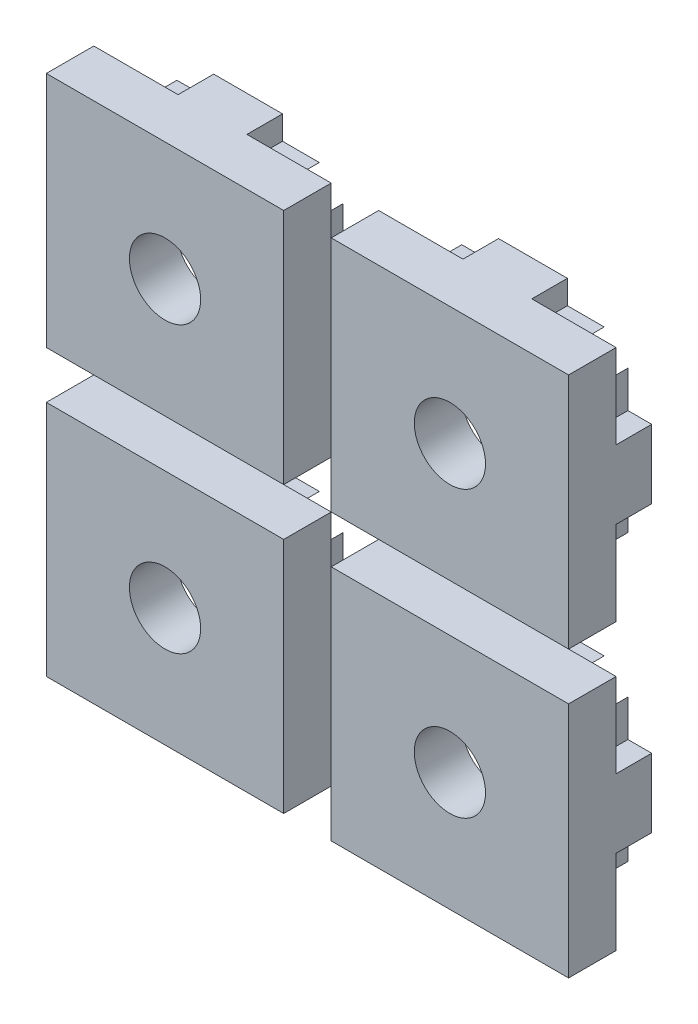
SolidWorks part; units mm, degrees
note: '?' marks a value the reader was unsure of.
ref_plane "Front Plane" through (0, 0, 0) normal (0, 0, 1) x (1, 0, 0)
ref_plane "Top Plane" through (0, 0, 0) normal (0, 1, 0) x (1, 0, 0)
ref_plane "Right Plane" through (0, 0, 0) normal (1, 0, 0) x (0, 0, -1)
ref_axis "Axis1" through (0, 0, -1.2) along (0, 0, 1)?
sketch "Sketch1" plane through (0, 0, 0) normal (0, 0, 1) x (1, 0, 0)
  line L1 (-5, -5) -> (5, -5)
  line L2 (-5, -5) -> (-5, 5)
  line L3 (-5, 5) -> (5, 5)
  line L4 (5, -5) -> (5, 5)
  line L5 (-5, -5) -> (5, 5) construction
  line L6 (-5, 5) -> (5, -5) construction
  circle A0 centre (0, 0) radius 1.5
  point P0 (0, 0)
  dimension "D3" = 3
  dimension "D1" = 10
  dimension "D2" = 10
extrude "Main" add sketch "Sketch1" along normal blind 2
sketch "Sketch2" plane through (0, 0, 0) normal (0, 0, -1) x (-1, 0, 0)
  line L0 (-5, 1.45) -> (-4, 1.45)
  line L1 (-5, -5) -> (-5, 5) construction
  line L2 (-4, 1.45) -> (-4, 3)
  line L3 (-4, -1.45) -> (-5, -1.45)
  line L4 (-5, 1.45) -> (-5, -1.45)
  line L5 (-4, 3) -> (-2, 1)
  line L6 (-2, 1) -> (-2, -1)
  line L7 (-2, -1) -> (-4, -3)
  line L8 (-4, -3) -> (-4, -1.45)
  line L9 (-5, 5) -> (5, 5) construction
  point P5 (-2, 0)
  dimension "D1" = 2.9
  dimension "D2" = 1
  dimension "D3" = 2
  dimension "D4" = 2
  dimension "D5" = 2
  dimension "D6" = 3
extrude "AntiRotationSystem" add sketch "Sketch2" along normal blind 1.5
pattern_circular "CirPattern1" count 4 over 360 about axis through (0, 0, 0) along (0, 0, 1) of "AntiRotationSystem"
pattern_linear "LPattern1" count 2 spacing 12 along (0, -1, 0) of bodies 103
pattern_linear "LPattern2" count 2 spacing 12 along (-1, 0, 0) of bodies 103 107
